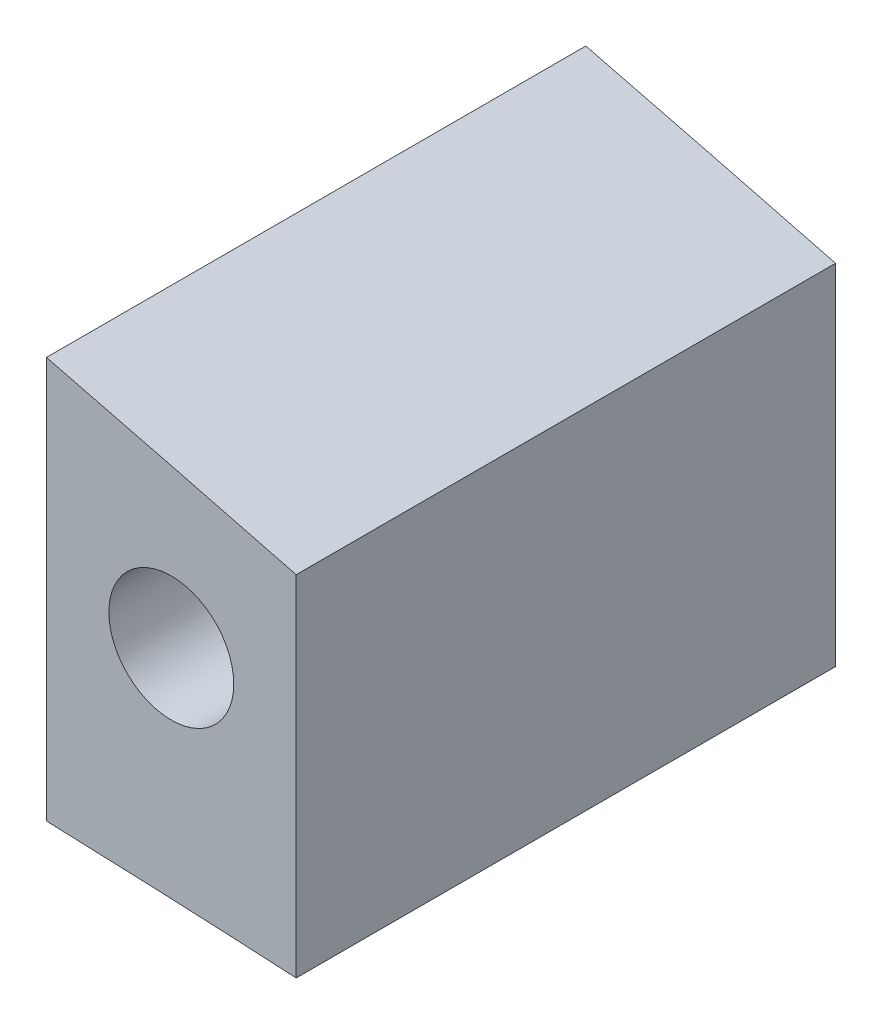
SolidWorks part; units mm, degrees
ref_plane "Front Plane" through (0, 0, 0) normal (0, 0, 1) x (1, 0, 0)
ref_plane "Top Plane" through (0, 0, 0) normal (0, 1, 0) x (1, 0, 0)
ref_plane "Right Plane" through (0, 0, 0) normal (1, 0, 0) x (0, 0, -1)
sketch "Sketch1" plane through (0, 0, 0) normal (0, 0, 1) x (1, 0, 0)
  spline S0 degree 3 poles (0.0006, 0.0001) (0.8106, 7.3592) (8.6491, 17.8566) (26.2867, 29.9752) (52.1111, 42.0692) (89.5976, 49.2908) (131.4008, 47.8848) (173.2567, 40.0411) (217.9611, 29.613) (256.9521, 19.5289) (290.3598, 8.711) (301.2732, 4.3828) (314.8169, -0.5162) (309.8463, 0.0001) knots 0 0 0 0 0.060864 0.113688 0.188609 0.312909 0.448482 0.557612 0.691544 0.852438 0.929756 0.976058 1 1 1 1
  spline S1 degree 3 poles (309.8463, 0.0001) (303.9568, 1.471) (293.9895, 2.094) (276.264, 4.5144) (260.8463, 5.4274) (235.8588, 7.8703) (205.1014, 8.8381) (157.7186, 9.0307) (110.4973, 6.1815) (66.5062, -0.5867) (36.4547, -6.0985) (15.3166, -6.1891) (1.2307, -6.9241) (0.0006, 0.0001) knots 0 0 0 0 0.057787 0.095275 0.171021 0.205339 0.335319 0.464904 0.658702 0.785512 0.893517 0.943092 1 1 1 1
extrude "Boss-Extrude1" add sketch "Sketch1" along normal blind 27.432
sketch "Sketch2" plane through (0, 0, 27.432) normal (0, 0, 1) x (1, 0, 0)
  line L1 (390.8807, -48.3469) -> (233.6463, -48.3469)
  line L2 (390.8807, -48.3469) -> (390.8807, 106.1594)
  line L3 (390.8807, 106.1594) -> (233.6463, 106.1594)
  line L4 (233.6463, -48.3469) -> (233.6463, 106.1594)
  circle A0 centre (20.32, 10.16) radius 6.35
  circle A1 centre (227.2963, 19.0501) radius 3.175
  dimension "D2" = 12.7
  dimension "D3" = 6.35
  dimension "D6" = 20.32
  dimension "D1" = 82.55
  dimension "D4" = 19.05
  dimension "D5" = 10.16
  dimension "D7" = 6.35
extrude "Cut-Extrude1" cut sketch "Sketch2" against normal through all
sketch "Sketch3" plane through (0, 0, 27.432) normal (0, 0, 1) x (1, 0, 0)
  line L0 (233.6463, 25.4528) -> (233.6463, 7.6905) construction
  line L1 (-72.2426, 80.4352) -> (220.9463, 80.4352)
  line L2 (-72.2426, 80.4352) -> (-72.2426, -57.5361)
  line L3 (-72.2426, -57.5361) -> (220.9463, -57.5361)
  line L4 (220.9463, 80.4352) -> (220.9463, -57.5361)
  dimension "D1" = 12.7
extrude "Cut-Extrude2" cut sketch "Sketch3" against normal through all
